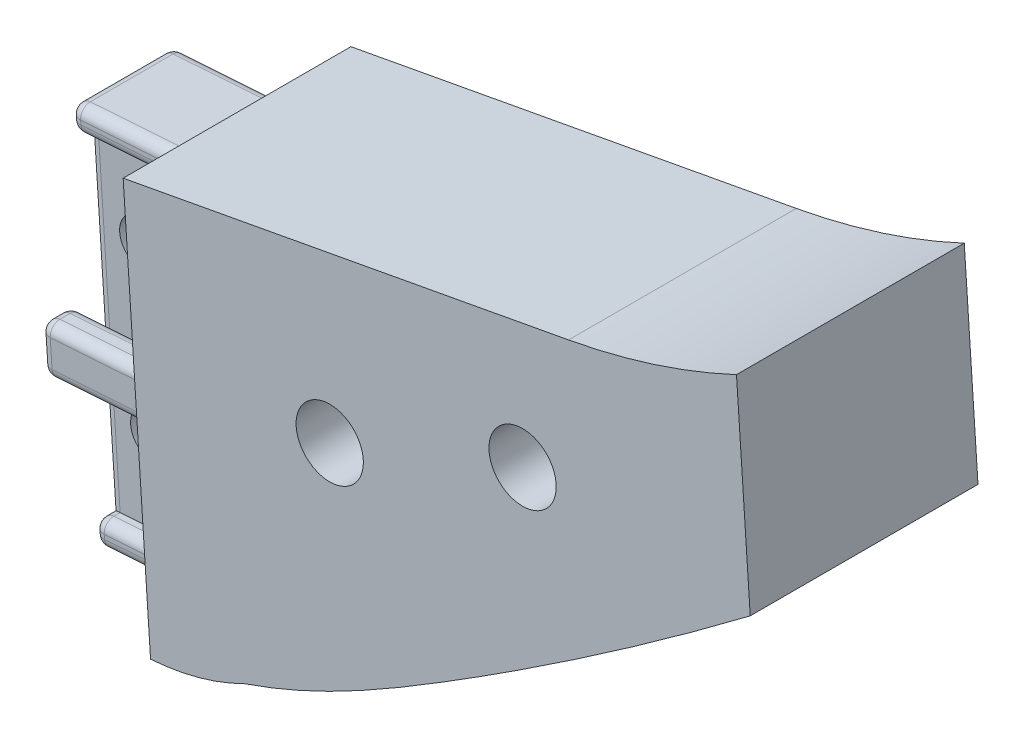
SolidWorks part; units mm, degrees
ref_plane "前视基准面" through (0, 0, 0) normal (0, 0, 1) x (1, 0, 0)
ref_plane "上视基准面" through (0, 0, 0) normal (0, 1, 0) x (1, 0, 0)
ref_plane "右视基准面" through (0, 0, 0) normal (1, 0, 0) x (0, 0, -1)
other "Configuration Table"
sketch "草图1" plane through (0, 0, 0) normal (0, 0, 1) x (1, 0, 0)
  line L0 (-47.0024, -50.0122) -> (-45.6747, -69.5254)
  line L2 (-104.9203, -82.6515) -> (-46.3385, -59.7688) construction
  line L3 (-63.2217, -55.2161) -> (-106.2441, -63.1951)
  line L4 (-106.2441, -63.1951) -> (-103.5965, -102.1079)
  circle A0 centre (-86.2911, -75.3747) radius 3.25
  circle A1 centre (-67.6619, -68.0979) radius 3.25
  arc A2 (-103.5965, -102.1079) -> (-94.5227, -99.6239) centre (-105.2096, -78.4007) ccw
  ellipse E0 centre (67.3628, 57.4319) end of major axis (68.0945, 56.7194) minor radius 0.6322 (68.1305, 56.762) -> (68.1502, 56.7917) ccw
  spline S0 degree 3 poles (-94.5227, -99.6239) (-94.3504, -99.5653) (-94.1783, -99.5059) (-92.6986, -98.9872) (-91.4002, -98.4778) (-88.845, -97.3809) (-87.5861, -96.7928) (-85.0984, -95.5532) (-83.8689, -94.9012) (-80.2189, -92.8772) (-77.8382, -91.4384) (-75.4727, -89.9735) knots 0 0 0 0 0.016429 0.016429 0.141429 0.141429 0.266429 0.266429 0.391429 0.391429 0.641429 0.641429 0.641429 0.641429
  spline S1 degree 3 poles (-75.4727, -89.9735) (-69.114, -86.0353) (-62.8774, -81.9021) (-53.0192, -74.9708) (-49.324, -72.2786) (-45.6747, -69.5254) knots 0 0 0 0 0.125 0.125 0.201402 0.201402 0.201402 0.201402
  spline S10 degree 3 poles (-47.0024, -50.0122) (-49.4134, -51.1396) (-51.8894, -52.1283) (-56.1365, -53.5303) (-57.8792, -54.0265) (-60.8276, -54.739) (-62.0219, -54.9935) (-63.2217, -55.2161) knots 0.829123 0.829123 0.829123 0.829123 0.875 0.875 0.90625 0.90625 0.927297 0.927297 0.927297 0.927297
  point P16 (-46.3385, -59.7688)
  dimension "D3" = 6.5
  dimension "D4" = 6.5
  dimension "D1" = 60
  dimension "D5" = 20
  dimension "D6" = 20
extrude "凸台-拉伸1" add sketch "草图1" along normal blind 22 contours L2 L4 A2 S0 S1 L0 A1 A0 | L4 L2 A0 A1 L0 S10 L3 region at (-80.0883, -65.2897, 0) region at (-78.2537, -81.5937, 0)
sketch "草图2" plane through (-110.0345, -7.4867, 0) normal (-0.9977, -0.0679, 0) x (0, 0, 1)
  line L0 (11, -57.34) -> (11, -93.34) construction
  line L1 (7.6, -57.34) -> (14.4, -57.34)
  line L2 (7.6, -57.34) -> (7.6, -93.34)
  line L3 (7.6, -93.34) -> (14.4, -93.34)
  line L4 (0, -55.8372) -> (0, -94.84)
  line L5 (0, -94.84) -> (22, -94.84)
  line L6 (22, -94.84) -> (22, -55.8372)
  line L7 (22, -55.8372) -> (0, -55.8372)
  line L8 (0, -55.8372) -> (0, -94.84)
  line L9 (0, -94.84) -> (22, -94.84)
  line L10 (22, -94.84) -> (22, -55.8372)
  line L11 (22, -55.8372) -> (0, -55.8372)
  line L12 (14.4, -57.34) -> (14.4, -93.34)
  line L13 (17, -73.0372) -> (20, -73.0372)
  line L14 (17, -73.0372) -> (17, -77.6372)
  line L15 (17, -77.6372) -> (20, -77.6372)
  line L16 (20, -73.0372) -> (20, -77.6372)
  line L17 (5, -77.6372) -> (2, -77.6372)
  line L18 (5, -73.0372) -> (5, -77.6372)
  line L19 (5, -73.0372) -> (2, -73.0372)
  line L20 (2, -73.0372) -> (2, -77.6372)
  dimension "D2" = 36
  dimension "D3" = 6.8
  dimension "D4" = 1.5
  dimension "D5" = 7.6
  dimension "D6" = 2.6
  dimension "D7" = 3
  dimension "D8" = 4.6
  dimension "D9" = 17.2
  dimension "D1" = 0
extrude "凸台-拉伸2" add sketch "草图2" along normal blind 11.3 contours L17 L20 L19 L18 | L2 L1 L12 L3 | L14 L13 L16 L15
sketch "草图3" plane through (-121.3084, -8.2537, 0) normal (-0.9977, -0.0679, 0) x (0, 0, 1)
  line L0 (7.6, -57.34) -> (14.4, -93.34)
  line L2 (9.5, -78.34) -> (12.5, -78.34)
  line L3 (9.5, -78.34) -> (9.5, -72.34)
  line L4 (7.6, -93.34) -> (14.4, -93.34)
  line L5 (14.4, -93.34) -> (14.4, -57.34)
  line L6 (14.4, -57.34) -> (7.6, -57.34)
  line L7 (7.6, -57.34) -> (7.6, -93.34)
  line L8 (7.6, -93.34) -> (14.4, -93.34)
  line L9 (14.4, -93.34) -> (14.4, -57.34)
  line L10 (14.4, -57.34) -> (7.6, -57.34)
  line L11 (7.6, -57.34) -> (7.6, -93.34)
  line L12 (9.5, -72.34) -> (12.5, -72.34)
  line L13 (12.5, -78.34) -> (12.5, -72.34)
  line L14 (9.5, -78.34) -> (12.5, -72.34) construction
  line L15 (9.5, -72.34) -> (12.5, -78.34) construction
  point P2 (11, -75.34)
  dimension "D2" = 6
  dimension "D3" = 3
  dimension "D1" = 0
extrude "切除-拉伸1" cut sketch "草图3" against normal blind 20 contours L2 L13 L12 L0 | L12 L3 L2 L0 region at (-116.2198, -83.043, 11.7143) region at (-116.1685, -83.7968, 10.2857)
sketch "草图4" plane through (0, 0, 14.4) normal (0, 0, 1) x (1, 0, 0)
  line L0 (-116.1942, -83.4199) -> (-104.9202, -82.6528)
  line L4 (-103.6984, -100.6113) -> (-106.1421, -64.6944)
  line L5 (-106.1421, -64.6944) -> (-117.4161, -65.4614)
  line L6 (-117.4161, -65.4614) -> (-114.9723, -101.3784)
  line L7 (-114.9723, -101.3784) -> (-103.6984, -100.6113)
  line L8 (-103.6984, -100.6113) -> (-106.1421, -64.6944)
  line L9 (-106.1421, -64.6944) -> (-117.4161, -65.4614)
  line L10 (-117.4161, -65.4614) -> (-114.9723, -101.3784)
  line L11 (-114.9723, -101.3784) -> (-103.6984, -100.6113)
  circle A0 centre (-111.9347, -75.3121) radius 2.25
  circle A1 centre (-110.8758, -90.8761) radius 2.25
  dimension "D2" = 4.5
  dimension "D3" = 4.5
  dimension "D5" = 6.5
  dimension "D6" = 7.8
  dimension "D7" = 7.8
  dimension "D4" = 6.5
  dimension "D1" = 0
extrude "切除-拉伸2" cut sketch "草图4" against normal blind 20 contours A1 | A0 region at (-111.9347, -75.3121, 14.4) region at (-110.8758, -90.8761, 14.4)
sketch "草图5" plane through (-121.3084, -8.2537, 0) normal (-0.9977, -0.0679, 0) x (0, 0, 1)
  line L0 (7.6, -57.34) -> (14.4, -93.34)
  line L2 (6, -90.94) -> (16, -90.94)
  line L3 (6, -90.94) -> (6, -59.74)
  line L4 (7.6, -93.34) -> (14.4, -93.34)
  line L5 (14.4, -93.34) -> (14.4, -57.34)
  line L6 (14.4, -57.34) -> (7.6, -57.34)
  line L7 (7.6, -57.34) -> (7.6, -93.34)
  line L8 (7.6, -93.34) -> (14.4, -93.34)
  line L9 (14.4, -93.34) -> (14.4, -57.34)
  line L10 (14.4, -57.34) -> (7.6, -57.34)
  line L11 (7.6, -57.34) -> (7.6, -93.34)
  line L12 (6, -59.74) -> (16, -59.74)
  line L13 (16, -90.94) -> (16, -59.74)
  line L14 (6, -90.94) -> (16, -59.74) construction
  line L15 (6, -59.74) -> (16, -90.94) construction
  line L16 (6, -57.34) -> (16, -57.34)
  line L17 (6, -57.34) -> (6, -93.34)
  line L18 (6, -93.34) -> (16, -93.34)
  line L19 (16, -57.34) -> (16, -93.34)
  line L20 (6, -57.34) -> (16, -93.34) construction
  line L21 (6, -93.34) -> (16, -57.34) construction
  point P2 (11, -75.34)
  point P9 (11, -75.34)
  line M12 (14.4, -93.34) -> (14.4, -57.34)
  line M14 (7.6, -57.34) -> (7.6, -93.34)
  dimension "D2" = 15.6
  dimension "D3" = 10
  dimension "D1" = 0
extrude "凸台-拉伸3" add sketch "草图5" against normal up to surface (11.3 mm away) contours L19 L2 L18 M12 | L17 L18 L2 M14 | L16 L17 L12 M14 | L19 L16 L9 L12 region at (-117.3346, -66.6587, 6.8) region at (-117.3346, -66.6587, 15.2) region at (-115.0538, -100.1812, 6.8) region at (-115.0538, -100.1812, 15.2) up to face at (-104.9202, -82.6528, 11)
fillet "圆角1" radius 1 20 edges at (-106.4209, -79.748, 9.5) (-106.4209, -79.748, 12.5) (-106.0136, -85.7342, 9.5) (-106.0136, -85.7342, 12.5) (-109.4982, -98.6004, 16) (-109.3353, -100.9949, 16) (-109.3353, -100.9949, 6) (-109.4982, -98.6004, 6) (-111.6162, -67.4724, 6) (-111.7791, -65.0779, 6) (-111.7791, -65.0779, 16) (-111.6162, -67.4724, 16) (-110.7135, -80.739, 5) (-110.4013, -85.3284, 5) (-110.4013, -85.3284, 2) (-110.7135, -80.739, 2) (-110.4013, -85.3284, 17) (-110.7135, -80.739, 17) (-110.4013, -85.3284, 20) (-110.7135, -80.739, 20)
fillet "圆角2" radius 1 44 edges at (-114.9922, -101.0862, 15.7071) (-114.9723, -101.3784, 11) (-114.9922, -101.0862, 6.2929) (-115.0538, -100.1812, 6) (-115.1153, -99.2761, 6.2929) (-115.1352, -98.9839, 7.3) (-116.1942, -83.4199, 7.6) (-117.2531, -67.8559, 7.3) (-117.273, -67.5637, 6.2929) (-117.3346, -66.6587, 6) (-117.3962, -65.7536, 6.2929) (-117.4161, -65.4614, 11) (-117.3962, -65.7536, 15.7071) (-117.3346, -66.6587, 16) (-117.273, -67.5637, 15.7071) (-117.2531, -67.8559, 14.7) (-116.1942, -83.4199, 14.4) (-115.1352, -98.9839, 14.7) (-115.1153, -99.2761, 15.7071) (-115.0538, -100.1812, 16) (-116.3779, -80.719, 12.2071) (-116.3978, -80.4268, 11) (-116.3779, -80.719, 9.7929) (-116.1942, -83.4199, 9.5) (-116.0104, -86.1208, 9.7929) (-115.9905, -86.413, 11) (-116.0104, -86.1208, 12.2071) (-116.1942, -83.4199, 12.5) (-116.0581, -85.4197, 4.7071) (-116.0382, -85.7119, 3.5) (-116.0581, -85.4197, 2.2929) (-116.1944, -83.4172, 2) (-116.3306, -81.4147, 2.2929) (-116.3505, -81.1225, 3.5) (-116.3306, -81.4147, 4.7071) (-116.1944, -83.4172, 5) (-116.3306, -81.4147, 17.2929) (-116.3505, -81.1225, 18.5) (-116.3306, -81.4147, 19.7071) (-116.1944, -83.4172, 20) (-116.0581, -85.4197, 19.7071) (-116.0382, -85.7119, 18.5) (-116.0581, -85.4197, 17.2929) (-116.1944, -83.4172, 17)
